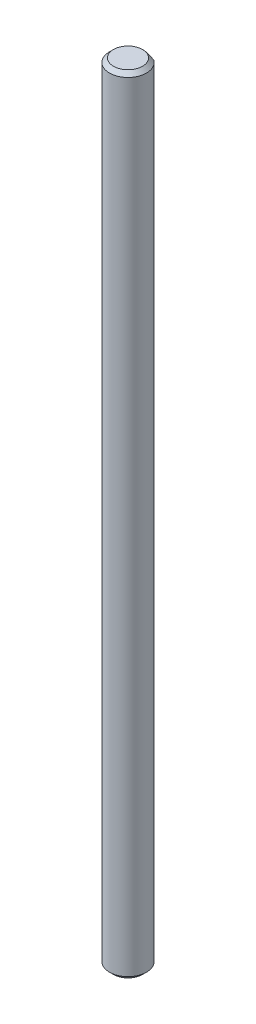
SolidWorks part; units mm, degrees
ref_plane "Front Plane" through (0, 0, 0) normal (0, 0, 1) x (1, 0, 0)
ref_plane "Top Plane" through (0, 0, 0) normal (0, 1, 0) x (1, 0, 0)
ref_plane "Right Plane" through (0, 0, 0) normal (1, 0, 0) x (0, 0, -1)
sketch "Sketch1" plane through (0, 0, 0) normal (0, 0, 1) x (1, 0, 0)
  line L0 (0, -50) -> (-1.85, -50)
  line L1 (-1.85, -50) -> (-2.35, -49.5)
  line L2 (-2.35, -49.5) -> (-2.35, 49.5)
  line L3 (-2.35, 49.5) -> (-1.85, 50)
  line L4 (-1.85, 50) -> (0, 50)
  line L5 (0, 50) -> (0, -50)
  dimension "D1" = 135
  dimension "D2" = 135
  dimension "D3" = 0.5
  dimension "D4" = 2.35
  dimension "D5" = 100
revolve "Revolve1" add sketch "Sketch1" angle 360 about L5
sketch "Sketch2" plane through (0, 50, 0) normal (0, 1, 0) x (1, 0, 0)
  line L0 (-1.4232, 1.87) -> (1.4232, 1.87)
  line L1 (0, -2.35) -> (0, 1.87) construction
  circle A0 centre (0, 0) radius 2.35 construction
  circle A1 centre (0, 0) radius 2.35
  circle M1 centre (0, 0) radius 1.85
  dimension "D1" = 4.22
extrude "Cut-Extrude1" cut sketch "Sketch2" against normal through all contours L0 A1 M1 region at (0, 50, -2.0638)
ref_axis "Axis1" through (0, -49.5, 0) along (0, 1, 0)
